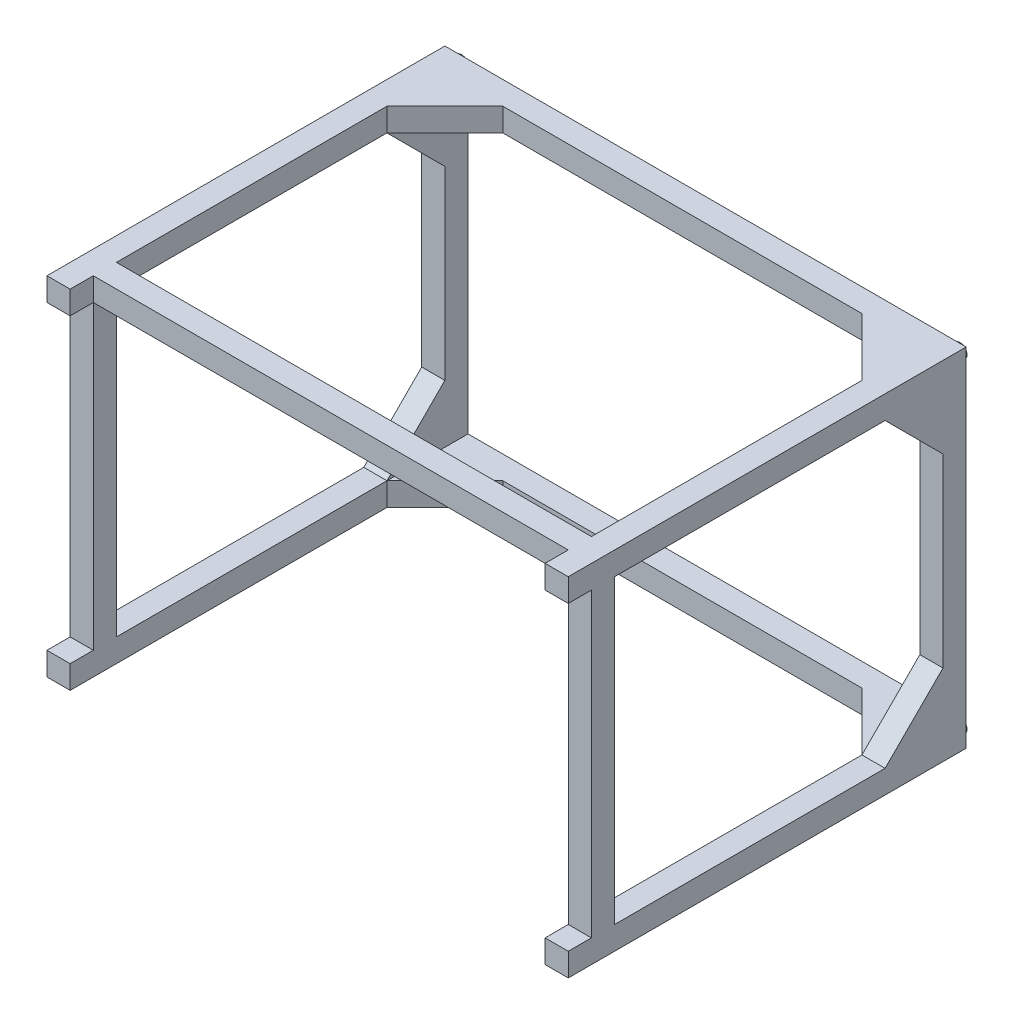
SolidWorks part; units mm, degrees
ref_plane "Front Plane" through (0, 0, 0) normal (0, 0, 1) x (1, 0, 0)
ref_plane "Top Plane" through (0, 0, 0) normal (0, 1, 0) x (1, 0, 0)
ref_plane "Right Plane" through (0, 0, 0) normal (1, 0, 0) x (0, 0, -1)
sketch "Sketch1" plane through (0, 0, 0) normal (0, 0, 1) x (1, 0, 0)
  line L0 (0, 0) -> (0, 600)
  line L1 (0, 600) -> (900, 600)
  line L2 (900, 600) -> (900, 0)
  line L3 (900, 0) -> (0, 0)
  line L4 (0, 40) -> (40, 40)
  line L5 (40, 40) -> (40, 0)
  line L6 (0, 560) -> (40, 560)
  line L7 (40, 560) -> (40, 600)
  line L8 (860, 600) -> (860, 560)
  line L9 (860, 560) -> (900, 560)
  line L10 (860, 0) -> (860, 40)
  line L11 (860, 40) -> (900, 40)
  line L12 (40, 560) -> (860, 560)
  line L13 (40, 40) -> (40, 560)
  line L14 (40, 40) -> (860, 40)
  line L15 (860, 40) -> (860, 560)
  point P3 (40, 0)
  point P6 (0, 40)
  point P9 (0, 560)
  point P11 (40, 600)
  point P12 (860, 600)
  point P13 (900, 560)
  point P14 (900, 40)
  point P15 (860, 0)
  dimension "D1" = 600
  dimension "D2" = 900
  dimension "D3" = 40
  dimension "D4" = 40
  dimension "D5" = 40
  dimension "D6" = 40
  dimension "D7" = 40
  dimension "D8" = 40
  dimension "D9" = 40
  dimension "D10" = 40
extrude "Boss-Extrude1" add sketch "Sketch1" along normal blind 687 contours L6 L7 L1 L0 region at (20, 580, 0)
extrude "Boss-Extrude2" add sketch "Sketch1<4>" along normal blind 687 separate body contours L8 L9 L2 L1 region at (880, 580, 0)
sketch "Sketch1<4>" plane through (0, 0, 0) normal (0, 0, 1) x (1, 0, 0) same geometry as "Sketch1"
extrude "Boss-Extrude3" add sketch "Sketch1<5>" along normal blind 687 separate body contours L5 L4 L0 L3 region at (20, 20, 0)
sketch "Sketch1<5>" plane through (0, 0, 0) normal (0, 0, 1) x (1, 0, 0) same geometry as "Sketch1"
extrude "Boss-Extrude4" add sketch "Sketch1<6>" along normal blind 687 separate body contours L11 L10 L3 L2 region at (880, 20, 0)
sketch "Sketch1<6>" plane through (0, 0, 0) normal (0, 0, 1) x (1, 0, 0) same geometry as "Sketch1"
extrude "Boss-Extrude5" add sketch "Sketch1<7>" along normal blind 40 contours L7 L12 L8 L1 region at (450, 580, 0)
sketch "Sketch1<7>" plane through (0, 0, 0) normal (0, 0, 1) x (1, 0, 0) same geometry as "Sketch1"
extrude "Boss-Extrude6" add sketch "Sketch1<8>" along normal blind 40 contours L4 L13 L6 L0 region at (20, 300, 0)
sketch "Sketch1<8>" plane through (0, 0, 0) normal (0, 0, 1) x (1, 0, 0) same geometry as "Sketch1"
extrude "Boss-Extrude7" add sketch "Sketch1<9>" along normal blind 40 contours L14 L5 L3 L10 region at (450, 20, 0)
sketch "Sketch1<9>" plane through (0, 0, 0) normal (0, 0, 1) x (1, 0, 0) same geometry as "Sketch1"
extrude "Boss-Extrude8" add sketch "Sketch1<10>" along normal blind 40 contours L15 L11 L2 L9 region at (880, 300, 0)
sketch "Sketch1<10>" plane through (0, 0, 0) normal (0, 0, 1) x (1, 0, 0) same geometry as "Sketch1"
sketch "Sketch2" plane through (0, 600, 0) normal (0, 1, 0) x (1, 0, 0)
  line L0 (40, -687) -> (40, -40) construction
  line L1 (40, -40) -> (860, -40) construction
  line L2 (40, -140) -> (140, -40)
  line L3 (860, -687) -> (860, -40) construction
  line L4 (760, -40) -> (860, -140)
  line L5 (40, -140) -> (40, -40)
  line L6 (40, -40) -> (140, -40)
  line L7 (760, -40) -> (860, -40)
  line L8 (860, -40) -> (860, -140)
  point P0 (40, -140)
  point P1 (140, -40)
  point P8 (760, -40)
  point P9 (860, -140)
  dimension "D1" = 100
  dimension "D2" = 100
  dimension "D3" = 100
  dimension "D4" = 100
extrude "Boss-Extrude9" add sketch "Sketch2" against normal blind 40
sketch "Sketch3" plane through (0, 0, 0) normal (-1, 0, 0) x (0, 0, 1)
  line L0 (687, 560) -> (40, 560) construction
  line L1 (687, 40) -> (40, 40) construction
  line L2 (40, 40) -> (40, 560) construction
  line L3 (40, 560) -> (40, 460)
  line L4 (40, 560) -> (140, 560)
  line L5 (40, 140) -> (40, 40)
  line L6 (40, 40) -> (140, 40)
  line L7 (40, 460) -> (140, 560)
  line L8 (40, 140) -> (140, 40)
  point P0 (140, 560)
  point P1 (140, 40)
  point P4 (40, 140)
  point P7 (40, 460)
  dimension "D1" = 100
  dimension "D2" = 100
  dimension "D3" = 100
  dimension "D4" = 100
extrude "Boss-Extrude10" add sketch "Sketch3" against normal blind 40
sketch "Sketch4" plane through (0, 0, 0) normal (0, -1, 0) x (1, 0, 0)
  line L0 (40, 140) -> (140, 40)
  line L1 (760, 40) -> (860, 140)
  line L2 (40, 40) -> (140, 40)
  line L3 (40, 140) -> (40, 40)
  line L4 (760, 40) -> (860, 40)
  line L5 (860, 40) -> (860, 140)
  point P0 (40, 140)
  point P1 (140, 40)
  point P3 (760, 40)
  point P5 (860, 140)
extrude "Boss-Extrude11" add sketch "Sketch4" against normal blind 40
sketch "Sketch5" plane through (900, 0, 0) normal (1, 0, 0) x (0, 0, -1)
  line L0 (-140, 560) -> (-40, 460)
  line L1 (-40, 460) -> (-40, 560)
  line L2 (-40, 560) -> (-140, 560)
  line L3 (-140, 40) -> (-40, 40)
  line L4 (-140, 40) -> (0, 40) construction
  line L5 (-687, 40) -> (-40, 40) construction
  line L6 (-40, 40) -> (-40, 140)
  line L7 (-40, 140) -> (-140, 40)
  point P0 (-140, 560)
  point P1 (-40, 460)
  point P3 (-40, 140)
  point P5 (-140, 40)
extrude "Boss-Extrude12" add sketch "Sketch5" against normal blind 40
sketch "Sketch6" plane through (860, 0, 0) normal (-1, 0, 0) x (0, 0, 1)
  line L0 (687, 600) -> (140, 600) construction
  line L1 (687, 560) -> (140, 560) construction
  line L2 (607, 600) -> (647, 600)
  line L3 (647, 600) -> (647, 560)
  line L4 (647, 560) -> (607, 560)
  line L5 (607, 560) -> (607, 600)
  point P0 (647, 600)
  point P1 (607, 600)
  point P4 (607, 560)
  point P6 (647, 560)
  dimension "D1" = 40
  dimension "D2" = 40
  dimension "D3" = 40
  dimension "D4" = 40
extrude "Boss-Extrude13" add sketch "Sketch6" along normal blind 820
sketch "Sketch7" plane through (0, 560, 0) normal (0, -1, 0) x (1, 0, 0)
  line L0 (0, 687) -> (0, 140) construction
  line L1 (0, 647) -> (0, 607)
  line L2 (0, 607) -> (40, 607)
  line L3 (40, 607) -> (40, 647)
  line L4 (40, 647) -> (0, 647)
  point P0 (40, 647)
  point P1 (40, 607)
  point P3 (0, 607)
  point P5 (0, 647)
extrude "Boss-Extrude14" add sketch "Sketch7" along normal blind 520
sketch "Sketch8" plane through (0, 560, 0) normal (0, -1, 0) x (1, 0, 0)
  line L0 (900, 687) -> (900, 140) construction
  line L1 (860, 647) -> (900, 647)
  line L2 (900, 647) -> (900, 607)
  line L3 (900, 607) -> (860, 607)
  line L4 (860, 607) -> (860, 647)
  point P0 (860, 647)
  point P1 (900, 647)
  point P3 (860, 607)
  point P6 (900, 607)
extrude "Boss-Extrude15" add sketch "Sketch8" along normal blind 520
sketch "Sketch9" plane through (0, 0, 0) normal (0, 0, -1) x (-1, 0, 0)
  line L0 (0, 600) -> (-900, 600) construction
  line L1 (-900, 600) -> (-900, 0) construction
  line L2 (-900, 0) -> (0, 0) construction
  line L3 (0, 0) -> (0, 600) construction
  circle A0 centre (-880, 580) radius 12.5
  circle A1 centre (-880, 20) radius 12.5
  circle A2 centre (-20, 580) radius 12.5
  circle A3 centre (-20, 20) radius 12.5
  point P0 (-880, 20)
  point P1 (-880, 580)
  point P2 (-20, 580)
  point P3 (-20, 20)
  dimension "D9" = 25
  dimension "D10" = 25
  dimension "D11" = 25
  dimension "D12" = 25
  dimension "D1" = 20
  dimension "D2" = 20
  dimension "D3" = 20
  dimension "D4" = 20
  dimension "D5" = 20
  dimension "D6" = 20
  dimension "D7" = 20
  dimension "D8" = 20
extrude "Boss-Extrude16" add sketch "Sketch9" along normal blind 9
